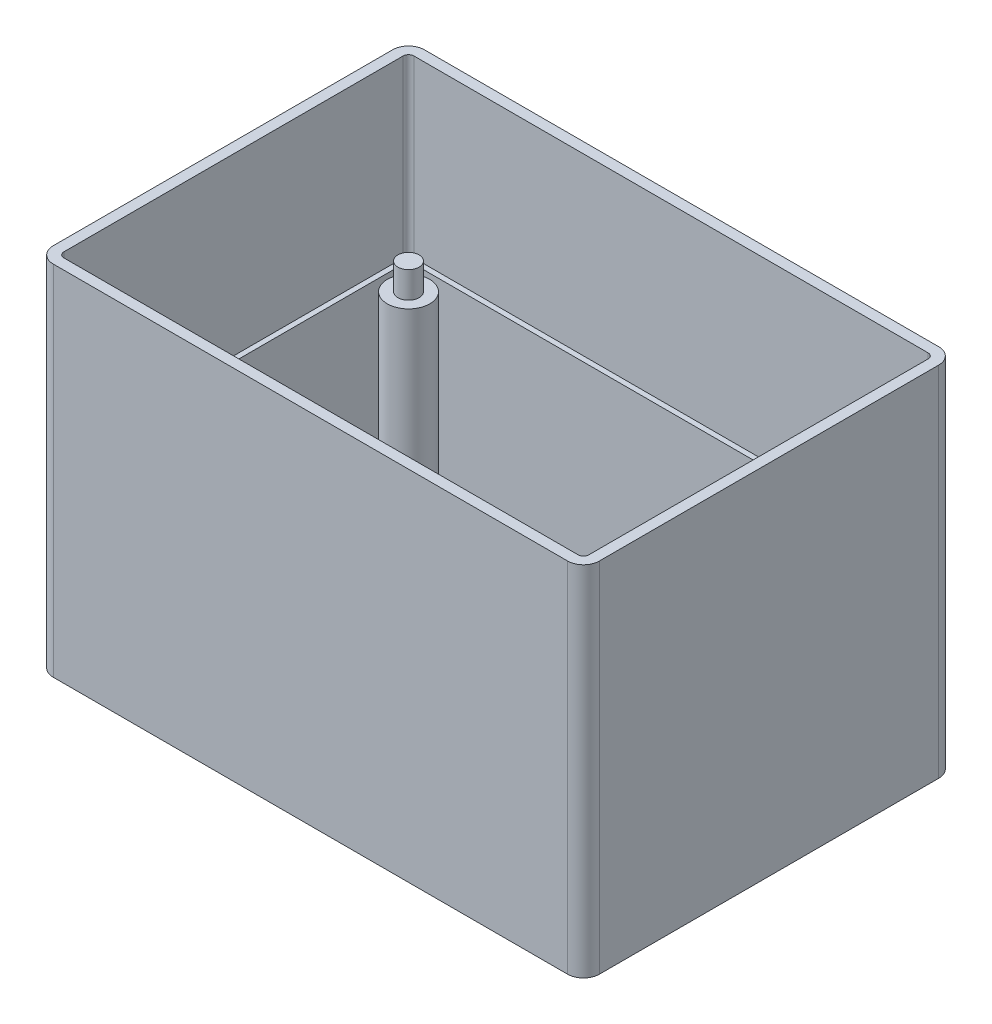
SolidWorks part; units mm, degrees
ref_plane "Front Plane" through (0, 0, 0) normal (0, 0, 1) x (1, 0, 0)
ref_plane "Top Plane" through (0, 0, 0) normal (0, 1, 0) x (1, 0, 0)
ref_plane "Right Plane" through (0, 0, 0) normal (1, 0, 0) x (0, 0, -1)
sketch "Sketch1" plane through (0, 0, 0) normal (0, 1, 0) x (1, 0, 0)
  line L0 (3, 2) -> (100, 2)
  line L1 (3, 0) -> (100, 0)
  line L2 (0, 3) -> (0, 67)
  line L3 (3, 70) -> (100, 70)
  line L4 (103, 3) -> (103, 67)
  line L5 (101, 3) -> (101, 67)
  line L6 (3, 68) -> (100, 68)
  line L7 (2, 3) -> (2, 67)
  line L8 (103, 35) -> (0, 35) construction
  line L9 (51.5, 70) -> (51.5, 0) construction
  line L10 (3, 67) -> (100, 67)
  line L11 (100, 3) -> (100, 67)
  line L12 (3, 3) -> (100, 3)
  line L13 (3, 3) -> (3, 67)
  arc A0 (0, 67) -> (3, 70) centre (3, 67) cw
  arc A1 (3, 0) -> (0, 3) centre (3, 3) cw
  arc A2 (103, 3) -> (100, 0) centre (100, 3) cw
  arc A3 (103, 67) -> (100, 70) centre (100, 67) ccw
  arc A4 (101, 3) -> (100, 2) centre (100, 3) cw
  arc A5 (101, 67) -> (100, 68) centre (100, 67) ccw
  arc A6 (2, 67) -> (3, 68) centre (3, 67) cw
  arc A7 (3, 2) -> (2, 3) centre (3, 3) cw
  circle A8 centre (95, 8) radius 2
  circle A9 centre (95, 62) radius 2
  circle A10 centre (8, 8) radius 2
  circle A11 centre (8, 62) radius 2
  circle A12 centre (95, 8) radius 4
  circle A13 centre (95, 62) radius 4
  circle A14 centre (8, 62) radius 4
  circle A15 centre (8, 8) radius 4
  arc A16 (100, 67) -> (100, 67) centre (100, 67) ccw
  arc A17 (100, 3) -> (100, 3) centre (100, 3) cw
  arc A18 (3, 3) -> (3, 3) centre (3, 3) cw
  arc A19 (3, 67) -> (3, 67) centre (3, 67) cw
  point P7 (0, 70)
  point P10 (0, 0)
  point P13 (103, 0)
  dimension "D3" = 3
  dimension "D5" = 8
  dimension "D6" = 8
  dimension "D1" = 103
  dimension "D2" = 70
  dimension "D4" = 2
  dimension "D7" = 2
  dimension "D8" = 2
  dimension "D9" = 2
  dimension "D10" = 2
  dimension "D11" = 1
extrude "Boss-Extrude4" add sketch "Sketch1" against normal blind 2.5 contours L13 L12 L11 L10 A13 A12 A14 A15 | A15 A10 | A10 | A7 L0 A4 L5 A5 L6 A6 L7 L12 L13 L10 L11 | L4 A3 L3 A0 L2 A1 L1 A2 L0 A7 L7 A6 L6 A5 L5 A4 | A8 | A12 A8 | A13 A9 | A9 | A14 A11 | A11 region at (2.377, 0, -2.377) region at (1.7593, 0, -1.7593) region at (51.5, 0, -35) region at (95, 0, -8) region at (95, 0, -62) region at (8, 0, -8) region at (8, 0, -62) region at (91.1131, 0, -8) region at (91.1131, 0, -62) region at (4.1131, 0, -62) region at (4.1131, 0, -8)
extrude "Boss-Extrude5" add sketch "Sketch1<8>" along normal blind 65 contours L4 A3 L3 A0 L2 A1 L1 A2 L0 A7 L7 A6 L6 A5 L5 A4 region at (1.7593, 0, -1.7593)
sketch "Sketch1<8>" plane through (0, 0, 0) normal (0, 1, 0) x (1, 0, 0) same geometry as "Sketch1"
extrude "Boss-Extrude6" add sketch "Sketch1<9>" along normal blind 32 contours A7 L0 A4 L5 A5 L6 A6 L7 L12 L13 L10 L11 | A14 A11 | A11 | A13 A9 | A9 | A12 A8 | A8 | A15 A10 | A10 region at (2.377, 0, -2.377) region at (95, 0, -8) region at (95, 0, -62) region at (8, 0, -8) region at (8, 0, -62) region at (91.1131, 0, -8) region at (91.1131, 0, -62) region at (4.1131, 0, -62) region at (4.1131, 0, -8)
sketch "Sketch1<9>" plane through (0, 0, 0) normal (0, 1, 0) x (1, 0, 0) same geometry as "Sketch1"
sketch "Sketch3" plane through (0, 32, 0) normal (0, 1, 0) x (1, 0, 0)
  circle A2 centre (8, 62) radius 2
  circle A3 centre (8, 62) radius 2
  point P0 (0, 0)
  dimension "D1" = 2
sketch "Sketch4" plane through (0, 32, 0) normal (0, 1, 0) x (1, 0, 0)
  circle A2 centre (8, 8) radius 2
  circle A3 centre (8, 8) radius 2
  dimension "D1" = 2
sketch "Sketch5" plane through (0, 32, 0) normal (0, 1, 0) x (1, 0, 0)
  circle A2 centre (95, 8) radius 2
  circle A3 centre (95, 8) radius 2
  dimension "D1" = 2
sketch "Sketch6" plane through (0, 32, 0) normal (0, 1, 0) x (1, 0, 0)
  circle A2 centre (95, 62) radius 2
  circle A3 centre (95, 62) radius 2
  dimension "D1" = 2
extrude "Boss-Extrude7" add sketch "Sketch3" along normal blind 5
extrude "Boss-Extrude8" add sketch "Sketch6" along normal blind 5 contours A3
extrude "Boss-Extrude9" add sketch "Sketch5" along normal blind 5 contours A3
extrude "Boss-Extrude10" add sketch "Sketch4" along normal blind 5 contours A3
sketch "Sketch11" plane through (100, 0, 0) normal (-1, 0, 0) x (0, 0, 1)
  line L0 (-35, 65) -> (-35, -2.5) construction
  line L2 (-67, 46) -> (-3, 46) construction
  line L3 (-67, -2.5) -> (-67, 65) construction
  line L4 (-3, -2.5) -> (-3, 65) construction
  line L5 (-3, 65) -> (-67, 65) construction
  line L6 (-3, -2.5) -> (-67, -2.5) construction
  line L8 (-39.5, 46) -> (-30.5, 46)
  line L9 (-39.5, 46) -> (-39.5, 42)
  line L10 (-39.5, 42) -> (-30.5, 42)
  line L11 (-30.5, 46) -> (-30.5, 42)
  dimension "D1" = 19
  dimension "D2" = 4.5
  dimension "D3" = 19
  dimension "D4" = 9
  dimension "D5" = 4
sketch "Sketch12" plane through (0, 0, 0) normal (-1, 0, 0) x (0, 0, 1)
  line L1 (-54.1719, 28.2561) -> (-14.1719, 28.2561)
  line L2 (-54.1719, 28.2561) -> (-54.1719, 10.1261)
  line L3 (-54.1719, 10.1261) -> (-14.1719, 10.1261)
  line L4 (-14.1719, 28.2561) -> (-14.1719, 10.1261)
  line L5 (-46.5401, 55.3654) -> (-21.5401, 55.3654)
  line L6 (-46.5401, 55.3654) -> (-46.5401, 30.3654)
  line L7 (-46.5401, 30.3654) -> (-21.5401, 30.3654)
  line L8 (-21.5401, 55.3654) -> (-21.5401, 30.3654)
  dimension "D1" = 18.13
  dimension "D2" = 40
  dimension "D3" = 25
  dimension "D4" = 25
